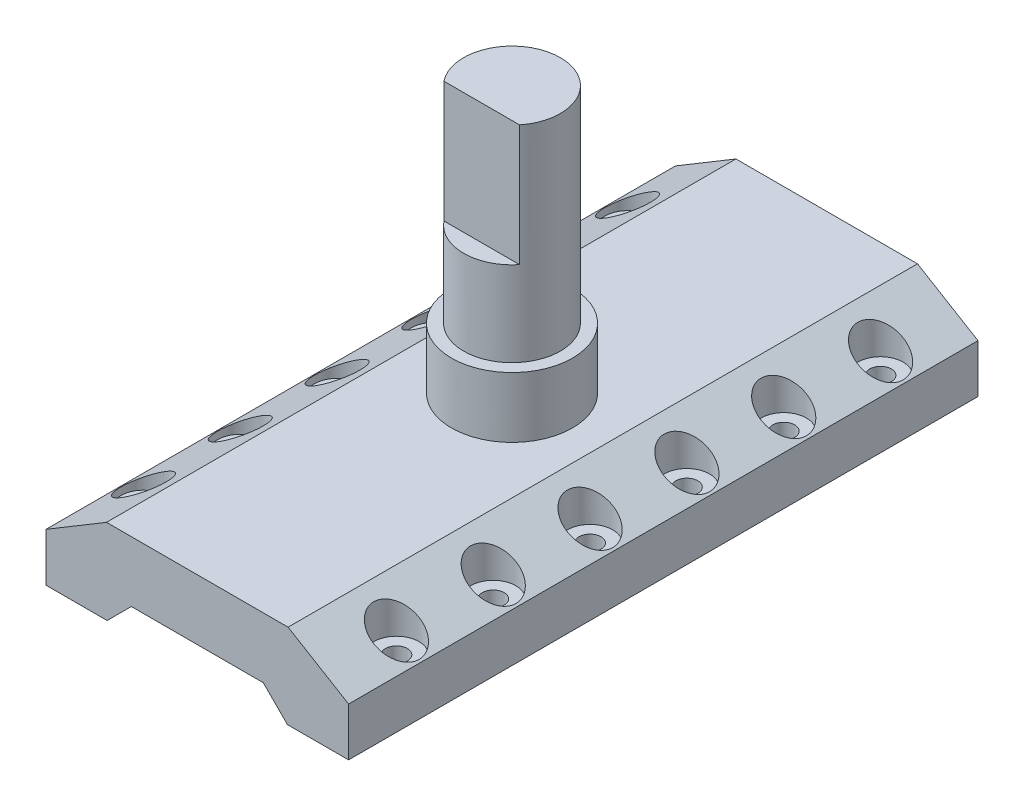
SolidWorks part; units mm, degrees
ref_plane "Front Plane" through (0, 0, 0) normal (0, 0, 1) x (1, 0, 0)
ref_plane "Top Plane" through (0, 0, 0) normal (0, 1, 0) x (1, 0, 0)
ref_plane "Right Plane" through (0, 0, 0) normal (1, 0, 0) x (0, 0, -1)
sketch "Sketch1" plane through (0, 0, 0) normal (0, 1, 0) x (1, 0, 0)
  line L1 (-12.5, -26) -> (12.5, -26)
  line L2 (-12.5, -26) -> (-12.5, 26)
  line L3 (-12.5, 26) -> (12.5, 26)
  line L4 (12.5, -26) -> (12.5, 26)
  line L5 (-12.5, -26) -> (12.5, 26) construction
  line L6 (-12.5, 26) -> (12.5, -26) construction
  point P0 (0, 0)
  dimension "D1" = 25
  dimension "D2" = 52
extrude "Boss-Extrude1" add sketch "Sketch1" along normal blind 7
sketch "Sketch2" plane through (0, 7, 0) normal (0, 1, 0) x (1, 0, 0)
  line L0 (-10.45, -20) -> (10.45, -20) construction
  line L1 (-12.5, -26) -> (12.5, -26) construction
  circle A0 centre (-10.45, -20) radius 0.9
  circle A1 centre (10.45, -20) radius 0.9
  point P4 (0, -20)
  dimension "D1" = 1.8
  dimension "D2" = 20.9
  dimension "D3" = 6
extrude "Cut-Extrude1" cut sketch "Sketch2" against normal through all
pattern_linear "LPattern1" count 6 spacing 8 along (0, 0, -1) of "Cut-Extrude1"
sketch "Sketch5" plane through (0, 7, 0) normal (0, 1, 0) x (1, 0, 0)
  circle A0 centre (0, 0) radius 4
  dimension "D1" = 8
extrude "Boss-Extrude2" add sketch "Sketch5" along normal blind 22
sketch "Sketch6" plane through (0, 7, 0) normal (0, 1, 0) x (1, 0, 0)
  circle A1 centre (0, 0) radius 4 construction
  circle A2 centre (0, 0) radius 5
  circle A3 centre (0, 0) radius 5
  circle A4 centre (0, 0) radius 4
  dimension "D1" = 1
extrude "Boss-Extrude3" add sketch "Sketch6" along normal blind 5
sketch "Sketch8" plane through (0, 29, 0) normal (0, 1, 0) x (1, 0, 0)
  line L0 (-3.1225, -2.5) -> (3.1225, -2.5)
  line L1 (0, -2.5) -> (0, 0) construction
  line L2 (0, 0) -> (0, -4) construction
  circle A0 centre (0, 0) radius 4 construction
  circle A2 centre (0, 0) radius 4
  arc A3 (-3.1225, -2.5) -> (3.1225, -2.5) centre (0, 0) ccw
  dimension "D1" = 0
  dimension "D2" = 2.5
  dimension "D3" = 0
extrude "Cut-Extrude2" cut sketch "Sketch8" against normal blind 10
sketch "Sketch9" plane through (0, 7, 0) normal (0, 1, 0) x (1, 0, 0)
  circle A0 centre (-10.45, 20) radius 1.875
  circle A2 centre (10.45, 20) radius 1.875
  dimension "D1" = 3.75
  dimension "D2" = 3.75
extrude "Cut-Extrude3" cut sketch "Sketch9" against normal blind 3.5
pattern_linear "LPattern2" count 6 spacing 8 along (0, 0, 1) of "Cut-Extrude3"
chamfer "Chamfer2" distance 3 distance2 5 2 edges at (-12.5, 7, 0) (12.5, 7, 0) first distance on face at (-12.5, 3.5, 0) first distance on face at (12.5, 3.5, 0)
sketch "Sketch10" plane through (0, 0, 0) normal (0, -1, 0) x (1, 0, 0)
  line L0 (12.5, -26) -> (-12.5, -26) construction
  line L1 (-7.45, -26) -> (7.45, -26)
  line L2 (-7.45, -26) -> (-7.45, 26)
  line L3 (-7.45, 26) -> (7.45, 26)
  line L4 (7.45, -26) -> (7.45, 26)
  line L5 (-12.5, 26) -> (12.5, 26) construction
  circle A0 centre (10.45, 20) radius 0.9 construction
  circle A1 centre (-10.45, 20) radius 0.9 construction
  dimension "D1" = 3
  dimension "D2" = 3
extrude "Cut-Extrude4" cut sketch "Sketch10" against normal blind 2
chamfer "Chamfer3" distance 2 angle 45 2 edges at (7.45, 2, 0) (-7.45, 2, 0)
